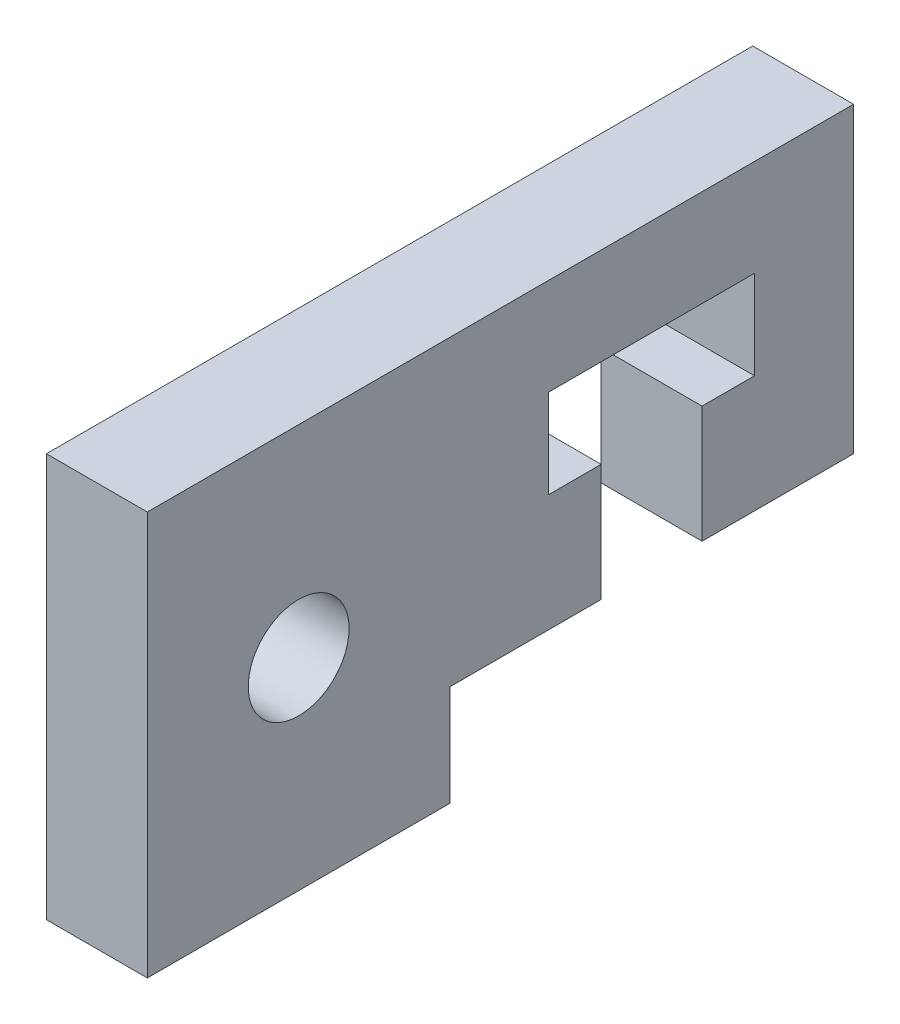
SolidWorks part; units mm, degrees
ref_plane "Front Plane" through (0, 0, 0) normal (0, 0, 1) x (1, 0, 0)
ref_plane "Top Plane" through (0, 0, 0) normal (0, 1, 0) x (1, 0, 0)
ref_plane "Right Plane" through (0, 0, 0) normal (1, 0, 0) x (0, 0, -1)
sketch "Sketch2" plane through (0, 0, 0) normal (1, 0, 0) x (0, 0, -1)
  line L0 (-4.7625, 6.35) -> (-4.7625, -6.35)
  line L1 (-4.7625, -6.35) -> (4.7625, -6.35)
  line L2 (4.7625, -6.35) -> (4.7625, -3.175)
  line L3 (17.4625, -3.175) -> (12.6942, -3.175)
  line L4 (17.4625, -3.175) -> (17.4625, 6.35)
  line L5 (17.4625, 6.35) -> (-4.7625, 6.35)
  line L6 (-19.474, 0) -> (-4.2216, 0) construction
  line L7 (12.6942, -3.175) -> (12.6942, 0.508)
  line L8 (12.6942, 0.508) -> (14.3452, 0.508)
  line L9 (14.3452, 0.508) -> (14.3452, 3.302)
  line L10 (14.3452, 3.302) -> (7.8682, 3.302)
  line L11 (7.8682, 3.302) -> (7.8682, 0.508)
  line L12 (7.8682, 0.508) -> (9.5192, 0.508)
  line L13 (9.5192, 0.508) -> (9.5192, -3.175)
  line L14 (9.5192, -3.175) -> (4.7625, -3.175)
  line L15 (11.1067, 0.9915) -> (11.1067, -22.7495) construction
  circle A0 centre (0, 0) radius 1.5875
  point P10 (-4.7625, 0)
  point P21 (11.1067, 3.302)
  dimension "D2" = 3.175
  dimension "D1" = 12.7
  dimension "D3" = 12.7
  dimension "D4" = 9.525
  dimension "D5" = 4.7625
  dimension "D6" = 22.225
  dimension "D7" = 6.477
  dimension "D8" = 3.175
  dimension "D9" = 6.3558
  dimension "D10" = 6.477
  dimension "D11" = 2.794
  dimension "D12" = 3.175
extrude "Boss-Extrude1" add sketch "Sketch2" along normal blind 1.5875 and the other way blind 1.5875
